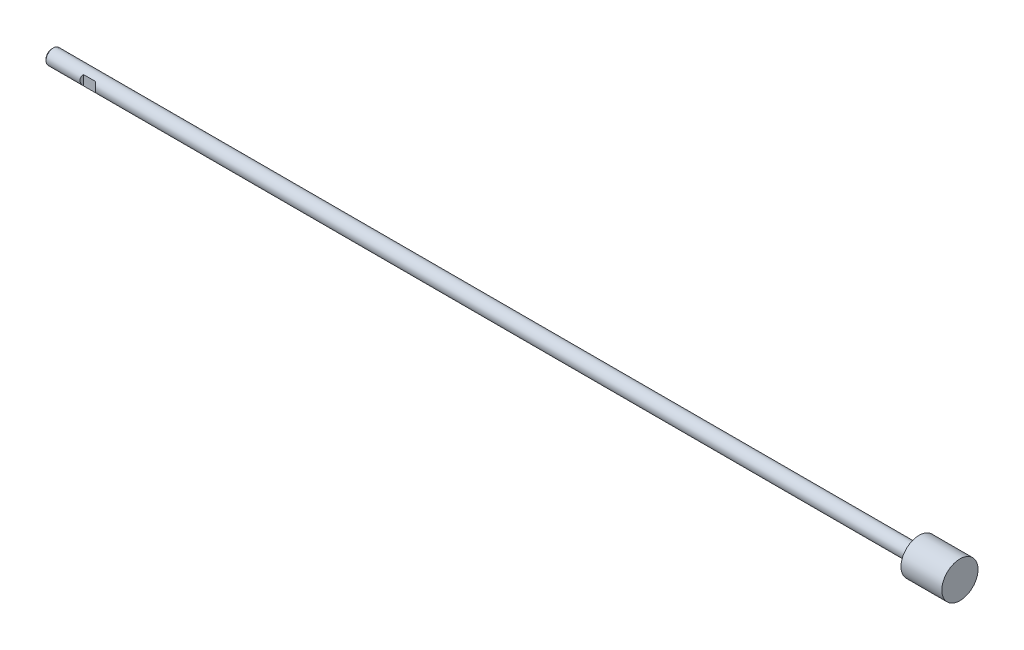
SolidWorks part; units mm, degrees
ref_plane "前视基准面" through (0, 0, 0) normal (0, 0, 1) x (1, 0, 0)
ref_plane "上视基准面" through (0, 0, 0) normal (0, 1, 0) x (1, 0, 0)
ref_plane "右视基准面" through (0, 0, 0) normal (1, 0, 0) x (0, 0, -1)
sketch "草图1" plane through (0, 0, 0) normal (0, 0, 1) x (1, 0, 0)
  line L0 (0, 0) -> (0, 3.233)
  line L1 (0, 3.233) -> (0.767, 4)
  line L2 (0.767, 4) -> (467, 4)
  line L3 (467, 4) -> (467, 9.75)
  line L4 (467, 9.75) -> (489, 9.75)
  line L5 (489, 9.75) -> (489, 0)
  line L6 (489, 0) -> (0, 0)
  line L7 (489, 0) -> (0, 0) construction
revolve "旋转1" add sketch "草图1" angle 360 about L7 reverse direction yes
cosmetic thread "装饰螺纹线1" parameters "D1"=18.75, "D2"=6.466
ref_plane "基准面4" through (28, 0, 0) normal (1, 0, 0) x (0, 0, -1)
ref_plane "基准面5" through (10, 0, 0) normal (1, 0, 0) x (0, 0, -1)
sketch "草图2" plane through (0, 0, 0) normal (0, 1, 0) x (1, 0, 0)
  line L0 (-5, -12) -> (35.4, -12)
  line L1 (35.4, -12) -> (26.4, -3)
  line L2 (26.4, -3) -> (20, -3)
  line L3 (20, -3) -> (18, -5)
  line L4 (18, -5) -> (18, -10)
  line L5 (18, -10) -> (-3, -10)
  line L6 (-3, -10) -> (-3, 10)
  line L7 (-3, 10) -> (18, 10)
  line L8 (18, 10) -> (18, 5)
  line L9 (18, 5) -> (20, 3)
  line L10 (20, 3) -> (26.4, 3)
  line L11 (26.4, 3) -> (35.4, 12)
  line L12 (35.4, 12) -> (-5, 12)
  line L13 (-5, 12) -> (-5, -12)
extrude "切除-拉伸1" cut sketch "草图2" along normal blind 3 and the other way blind 3
ref_plane "基准面6" through (0, 0, 0) normal (0, -0.7071, 0.7071) x (1, 0, 0)
ref_plane "基准面7" through (0, 0, 0) normal (0, -0.7071, -0.7071) x (-1, 0, 0)
ref_plane "nut-rod XY" through (10, 0, 0) normal (-1, 0, 0) x (0, 0, 1)
ref_plane "nut-rod XZ" through (0, 0, 0) normal (0, 1, 0) x (1, 0, 0)
ref_plane "nut-rod YZ" through (0, 0, 0) normal (0, 0, -1) x (-1, 0, 0)
ref_axis "nut-rod X" through (10, 0, 80.9) along (0, 0, -1)
ref_axis "nut-rod Y" through (10, 50, 0) along (0, -1, 0)
ref_axis "nut-rod Z" through (-80.9, 0, 0) along (1, 0, 0)
sketch3d "nut-rod"
  point P0 (10, 0, 0)
ref_plane "rod XY" through (28, 0, 0) normal (-1, 0, 0) x (0, 0, 1)
ref_plane "rod XZ" through (0, 0, 0) normal (0, 1, 0) x (1, 0, 0)
ref_plane "rod YZ" through (0, 0, 0) normal (0, 0, -1) x (-1, 0, 0)
ref_axis "rod X" through (28, 0, 80.9) along (0, 0, -1)
ref_axis "rod Y" through (28, 50, 0) along (0, -1, 0)
ref_axis "rod Z" through (-80.9, 0, 0) along (1, 0, 0)
sketch3d "rod"
  point P0 (28, 0, 0)
